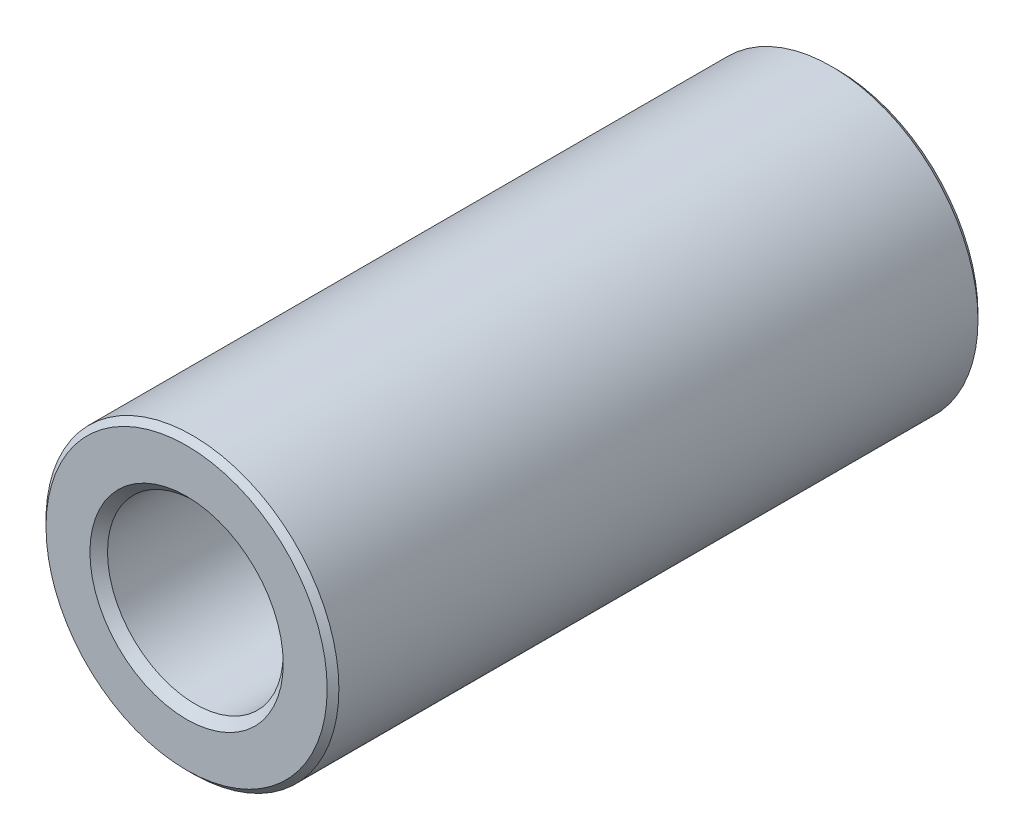
SolidWorks part; units mm, degrees
ref_plane "Front Plane" through (0, 0, 0) normal (0, 0, 1) x (1, 0, 0)
ref_plane "Top Plane" through (0, 0, 0) normal (0, 1, 0) x (1, 0, 0)
ref_plane "Right Plane" through (0, 0, 0) normal (1, 0, 0) x (0, 0, -1)
sketch "Sketch1" plane through (0, 0, 0) normal (0, 0, 1) x (1, 0, 0)
  circle A0 centre (0, 0) radius 2.25 construction
  circle A1 centre (0, 0) radius 1.35 construction
  point P4 (0, 2.25)
  dimension "ID" = 2.7
  dimension "OD" = 4.5
sketch "Sketch2" plane through (0, 0, 0) normal (1, 0, 0) x (0, 0, -1)
  line L0 (-5, 2.25) -> (5, 2.25) construction
  dimension "Length" = 10
sketch "Sketch3" plane through (0, 0, 0) normal (0, 0, 1) x (1, 0, 0)
  circle A0 centre (0, 0) radius 1.35 construction
  circle A1 centre (0, 0) radius 2.25 construction
  circle A2 centre (0, 0) radius 1.35
  circle A3 centre (0, 0) radius 2.25
extrude "Boss-Extrude1" add sketch "Sketch3" against normal up to vertex (5 mm away) and the other way up to vertex (5 mm away) up to point (0, 2.25, -5) other way up to point (0, 2.25, 5)
chamfer "Chamfer1" distance 0.09 angle 45 2 edges at (2.25, 0, 5) (2.25, 0, -5)
chamfer "Chamfer2" distance 0.135 angle 45 2 edges at (1.35, 0, 5) (1.35, 0, -5)
equation "\"D1@Chamfer1\"=(\"OD@Sketch1\"-\"ID@Sketch1\")*0.05"
equation "\"D1@Chamfer2\"=(\"OD@Sketch1\"-\"ID@Sketch1\")*0.075"
